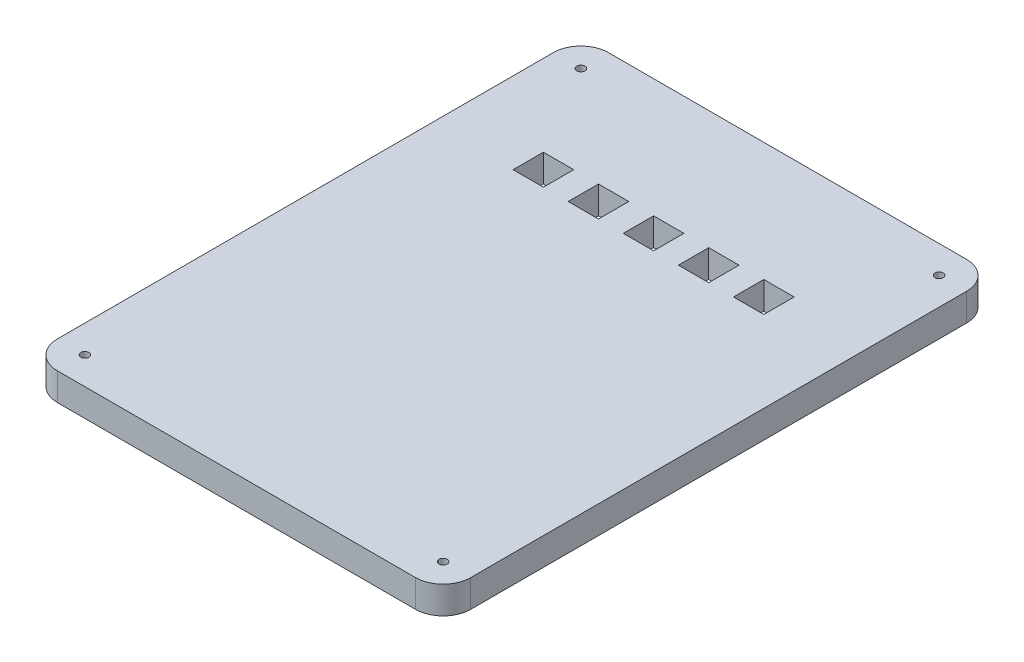
SolidWorks part; units mm, degrees
ref_plane "Спереди" through (0, 0, 0) normal (0, 0, 1) x (1, 0, 0)
ref_plane "Сверху" through (0, 0, 0) normal (0, 1, 0) x (1, 0, 0)
ref_plane "Справа" through (0, 0, 0) normal (1, 0, 0) x (0, 0, -1)
sketch "Эскиз1" plane through (0, 0, 0) normal (0, 1, 0) x (1, 0, 0)
  line L1 (75, -100) -> (-75, -100)
  line L2 (75, -100) -> (75, 100)
  line L3 (75, 100) -> (-75, 100)
  line L4 (-75, -100) -> (-75, 100)
  line L5 (75, -100) -> (-75, 100) construction
  line L6 (75, 100) -> (-75, -100) construction
  point P0 (0, 0)
  dimension "D1" = 200
  dimension "D2" = 150
extrude "Бобышка-Вытянуть1" add sketch "Эскиз1" along normal mid plane 10
fillet "Скругление1" radius 10 4 edges at (-75, 0, -100) (75, 0, -100) (75, 0, 100) (-75, 0, 100)
sketch "Эскиз2" plane through (0, 5, 0) normal (0, 1, 0) x (1, 0, 0)
  line L0 (0, 0) -> (0, -33.246) construction
  line L1 (0, 0) -> (-47.6996, 0) construction
  circle A0 centre (-65, 90) radius 1.5
  circle A1 centre (-65, -90) radius 1.5
  circle A2 centre (65, -90) radius 1.5
  circle A3 centre (65, 90) radius 1.5
extrude "Вырез-Вытянуть1" cut sketch "Эскиз2" against normal up to surface (10 mm away) up to face at (0, -5, 0)
sketch "Эскиз3" plane through (0, 5, 0) normal (0, 1, 0) x (1, 0, 0)
  line L0 (-34.5, 56.8905) -> (-34.5, 44.834)
  line L1 (45.5, 45.8905) -> (34.5, 45.8905)
  line L2 (45.5, 45.8905) -> (45.5, 56.8905)
  line L3 (45.5, 56.8905) -> (34.5, 56.8905)
  line L4 (-45.5, 45.8905) -> (-45.5, 56.8905)
  line L5 (45.5, 45.8905) -> (34.5, 47.2202) construction
  line L6 (45.5, 56.8905) -> (34.5, 55.5609) construction
  line L7 (-25.5, 56.8905) -> (-25.5, 45.8905)
  line L8 (34.5, 56.8905) -> (34.5, 45.8905)
  line L9 (25.5, 56.8905) -> (25.5, 45.8905)
  line L10 (14.5, 56.8905) -> (14.5, 45.8905)
  line L11 (5.5, 56.8905) -> (5.5, 45.8905)
  line L12 (-5.5, 56.8905) -> (-5.5, 45.8905)
  line L13 (-14.5, 56.8905) -> (-14.5, 45.8905)
  line L14 (-34.5, 56.8905) -> (-45.5, 56.8905)
  line L15 (-34.5, 55.5609) -> (-45.5, 56.8905) construction
  line L16 (-34.5, 47.2202) -> (-45.5, 45.8905) construction
  line L17 (-34.5, 45.8905) -> (-45.5, 45.8905)
  line L18 (-14.5, 56.8905) -> (-25.5, 56.8905)
  line L19 (-14.5, 53.1433) -> (-25.5, 54.473) construction
  line L20 (-14.5, 49.6378) -> (-25.5, 48.3081) construction
  line L21 (-14.5, 45.8905) -> (-25.5, 45.8905)
  line L22 (5.5, 56.8905) -> (-5.5, 56.8905)
  line L23 (5.5, 52.0554) -> (-5.5, 50.7257) construction
  line L24 (5.5, 50.7257) -> (-5.5, 52.0554) construction
  line L25 (5.5, 45.8905) -> (-5.5, 45.8905)
  line L26 (25.5, 56.8905) -> (14.5, 56.8905)
  line L27 (25.5, 54.473) -> (14.5, 53.1433) construction
  line L28 (25.5, 48.3081) -> (14.5, 49.6378) construction
  line L29 (25.5, 45.8905) -> (14.5, 45.8905)
  point P0 (0, 51.3905)
  point P14 (25.5, 51.3905)
  dimension "D1" = 11
  dimension "D2" = 91
  dimension "D3" = 11
  dimension "D4" = 9
  dimension "D5" = 11
  dimension "D6" = 9
  dimension "D7" = 11
  dimension "D8" = 9
  dimension "D9" = 11
  dimension "D10" = 9
extrude "Вырез-Вытянуть2" cut sketch "Эскиз3" against normal up to surface (10 mm away) contours L17 L0 L14 L4 | L21 L13 L18 L7 | L25 L11 L22 L12 | L29 L9 L26 L10 | L3 L8 L1 L2 region at (-40, 5, -51.3905) region at (40, 5, -51.3905) region at (-20, 5, -51.3905) region at (20, 5, -51.3905) region at (0, 5, -51.3905) up to face at (65, -5, -88.5)
